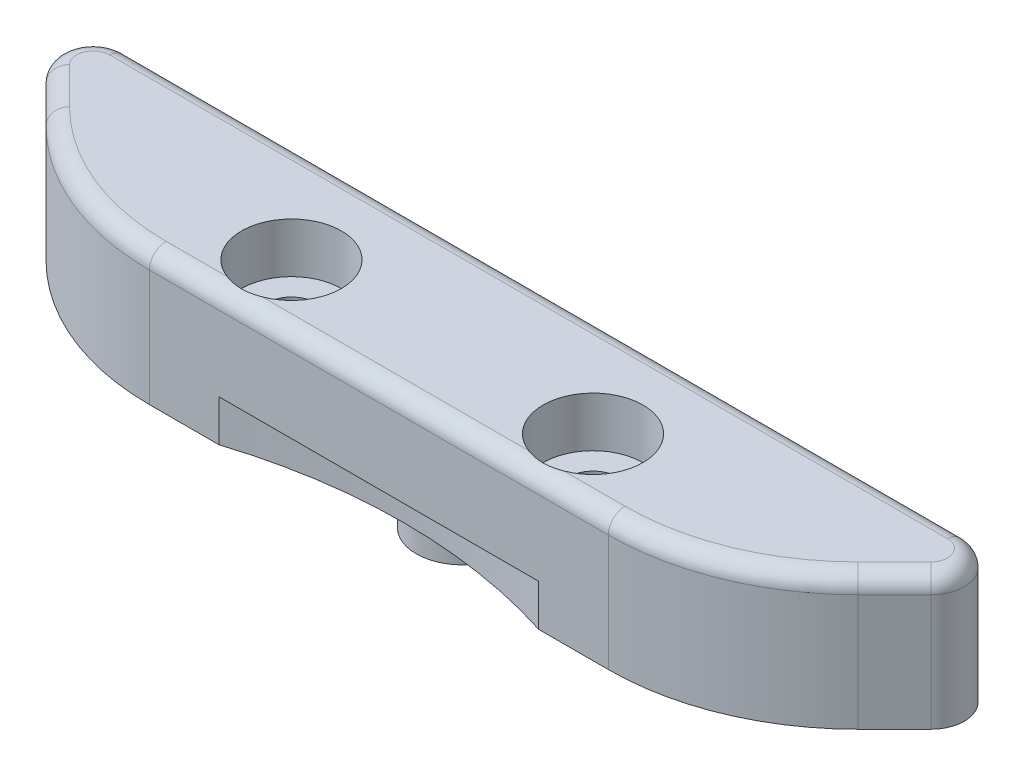
SolidWorks part; units mm, degrees
ref_plane "Front Plane" through (0, 0, 0) normal (0, 0, 1) x (1, 0, 0)
ref_plane "Top Plane" through (0, 0, 0) normal (0, 1, 0) x (1, 0, 0)
ref_plane "Right Plane" through (0, 0, 0) normal (1, 0, 0) x (0, 0, -1)
sketch "草图1" plane through (0, 0, 0) normal (0, 1, 0) x (1, 0, 0)
  line L0 (-9.0587, 33.8074) -> (0, 0) construction
  line L1 (0, 0) -> (0, 35) construction
  arc A0 (0, 35) -> (-9.0587, 33.8074) centre (0, 0) ccw
  circle A1 centre (0, 0) radius 31
  circle A2 centre (-9.0587, 33.8074) radius 3
  circle A3 centre (0, 35) radius 3
  dimension "D1" = 35
  dimension "D3" = 31
  dimension "D4" = 6
  dimension "D2" = 15
sketch "草图2" plane through (0, 0, 0) normal (0, 1, 0) x (1, 0, 0)
  line L0 (0, 0) -> (0, 35) construction
  line L1 (0, 30) -> (20, 30)
  line L2 (20, 30) -> (32.7105, 42.7105)
  arc A0 (0, 30) -> (0, -30) centre (0, 0) ccw
  dimension "D1" = 30
  dimension "D2" = 20
  dimension "D3" = 135
sketch "草图3" plane through (0, 0, 0) normal (0, 1, 0) x (1, 0, 0)
  line L0 (0, -1000) -> (0, 49000) construction
  line L1 (-20, 30) -> (20, 30)
  line L2 (20, 30) -> (32.7105, 42.7105) construction
  line L3 (20, 30) -> (30, 40)
  line L4 (30, 40) -> (-30, 40)
  line L5 (-20, 30) -> (-30, 40)
  line L6 (0, 30) -> (20, 30) construction
  point P13 (0, 40)
  point P14 (0, 30)
  dimension "D1" = 10
extrude "凸台-拉伸1" add sketch "草图3" along normal blind 8
sketch "草图4" plane through (0, 0, 0) normal (0, -1, 0) x (1, 0, 0)
  circle A0 centre (0, 0) radius 31.5
  dimension "D1" = 63
extrude "切除-拉伸1" cut sketch "草图4" against normal blind 2.5
sketch "草图5" plane through (0, 8, 0) normal (0, 1, 0) x (1, 0, 0)
  line L0 (0, -1000) -> (0, 49000) construction
  circle A0 centre (-9.0587, 33.8074) radius 1.5
  circle A1 centre (9.0587, 33.8074) radius 1.5
  dimension "D1" = 3
sketch "草图6" plane through (0, 8, 0) normal (0, 1, 0) x (1, 0, 0)
  circle A0 centre (-9.0587, 33.8074) radius 3
  circle A1 centre (9.0587, 33.8074) radius 3
  dimension "D1" = 6
extrude "切除-拉伸2" cut sketch "草图5" against normal through all
extrude "切除-拉伸3" cut sketch "草图6" against normal blind 3
sketch "草图7" plane through (0, 0, 0) normal (0, -1, 0) x (1, 0, 0)
  circle A0 centre (0, -35) radius 2.75
  dimension "D1" = 5.5
extrude "凸台-拉伸2" add sketch "草图7" along normal blind 2
fillet "圆角1" radius 15 2 edges at (20, 4, -30) (-20, 4, -30)
fillet "圆角2" radius 2 2 edges at (30, 4, -40) (-30, 4, -40)
fillet "圆角3" radius 1 8 edges at (-19.527, 8, -31.1418) (-25.4896, 8, -35.4896) (-27.0193, 8, -38.7654) (0, 8, -40) (27.0193, 8, -38.7654) (25.4896, 8, -35.4896) (19.527, 8, -31.1418) (0, 8, -30)
